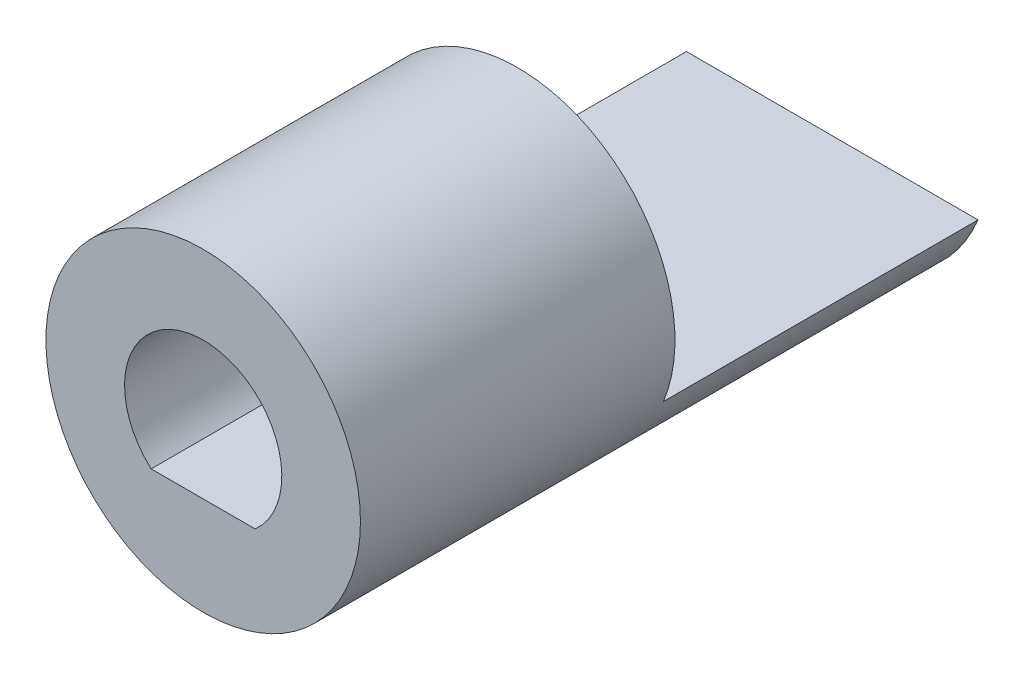
SolidWorks part; units mm, degrees
ref_plane "Front Plane" through (0, 0, 0) normal (0, 0, 1) x (1, 0, 0)
ref_plane "Top Plane" through (0, 0, 0) normal (0, 1, 0) x (1, 0, 0)
ref_plane "Right Plane" through (0, 0, 0) normal (1, 0, 0) x (0, 0, -1)
sketch "Sketch1" plane through (0, 0, 0) normal (0, 0, 1) x (1, 0, 0)
  line L0 (-4.2001, -4.7625) -> (4.2001, -4.7625)
  line L1 (-11.7732, -4.7625) -> (11.7732, -4.7625)
  arc A0 (4.2001, -4.7625) -> (-4.2001, -4.7625) centre (0, 0) ccw
  circle A1 centre (0, 0) radius 12.7
  dimension "D1" = 12.7
  dimension "D3" = 25.4
  dimension "D2" = 4.7625
extrude "Boss-Extrude1" add sketch "Sketch1" along normal blind 25.4 contours L1 A1 L0 | L1 A1 A0 region at (0, -8.0417, 0) region at (-7.9867, -4.4543, 0)
extrude "Boss-Extrude2" add sketch "Sketch1<4>" against normal blind 25.4 contours L1 A1 L0 region at (0, -8.0417, 0)
sketch "Sketch1<4>" plane through (0, 0, 0) normal (0, 0, 1) x (1, 0, 0) same geometry as "Sketch1"
